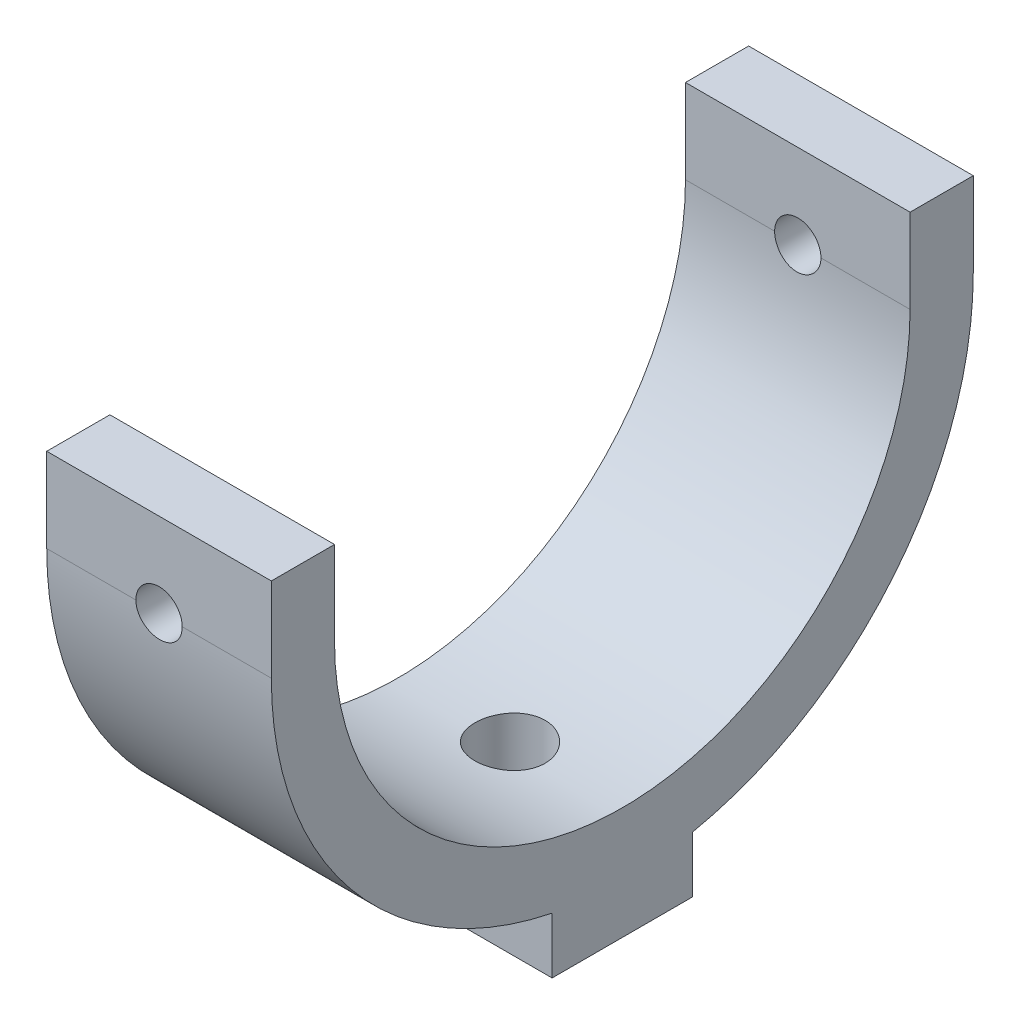
SolidWorks part; units mm, degrees
ref_plane "Front Plane" through (0, 0, 0) normal (0, 0, 1) x (1, 0, 0)
ref_plane "Top Plane" through (0, 0, 0) normal (0, 1, 0) x (1, 0, 0)
ref_plane "Right Plane" through (0, 0, 0) normal (1, 0, 0) x (0, 0, -1)
sketch "Sketch1" plane through (0, 0, 0) normal (1, 0, 0) x (0, 0, -1)
  line L3 (-5, -24.4949) -> (-5, -28.4949)
  line L4 (-5, -28.4949) -> (5, -28.4949)
  line L5 (5, -24.4949) -> (5, -28.4949)
  line L8 (25, 0) -> (25, 6)
  line L9 (25, 6) -> (20.5, 6)
  line L10 (20.5, 0) -> (20.5, 6)
  line L12 (-20.5, 0) -> (-20.5, 6)
  line L13 (-20.5, 6) -> (-25, 6)
  line L14 (-25, 0) -> (-25, 6)
  arc A0 (-25, 0) -> (-5, -24.4949) centre (0, 0) ccw
  arc A1 (5, -24.4949) -> (25, 0) centre (0, 0) ccw
  arc A2 (-20.5, 0) -> (20.5, 0) centre (0, 0) ccw
  dimension "D1" = 25
  dimension "D4" = 41
  dimension "D2" = 10
  dimension "D3" = 4
  dimension "D5" = 6
extrude "Boss-Extrude1" add sketch "Sketch1" along normal blind 16
sketch "Sketch5" plane through (0, 0, -25) normal (0, 0, -1) x (-1, 0, 0)
  line L0 (-16, 0) -> (0, 0) construction
  circle A0 centre (-8, 0) radius 1.65
  dimension "D1" = 3.3
extrude "Cut-Extrude1" cut sketch "Sketch5" against normal through all
sketch "Sketch6" plane through (0, -28.4949, 0) normal (0, -1, 0) x (1, 0, 0)
  line L0 (16, 5) -> (16, -5) construction
  line L1 (16, -5) -> (0, -5) construction
  point P0 (8, 0)
  point P1 (0, 0)
  point P4 (16, 0)
  point P5 (0, 0)
  point P8 (8, -5)
hole_wizard "M6x1.0 Tapped Hole1" positions "Sketch7" profile "Sketch8" tap size "M6x1.0" standard "BSI" end condition through all
sketch "Sketch7" plane through (0, -28.4949, 0) normal (0, -1, 0) x (-1, 0, 0)
  point P0 (-8, 0)
sketch "Sketch8" plane through (8, -28.4949, 0) normal (1, 0, 0) x (0, 0, -1)
  line L0 (0, 0) -> (0, 34.4949)
  line L1 (0, 34.4949) -> (2.5, 34.4949)
  line L2 (2.5, 34.4949) -> (2.5, 0)
  line L5 (2.5, 0) -> (0, 0)
  line L11 (0, -6.35) -> (0, 107.95) construction
  dimension "Thru Tap Drill Dia." = 5
  dimension "Thru Tap Drill Depth" = 34.4949
cosmetic thread "Hole Thread1" parameters "D2"=6
